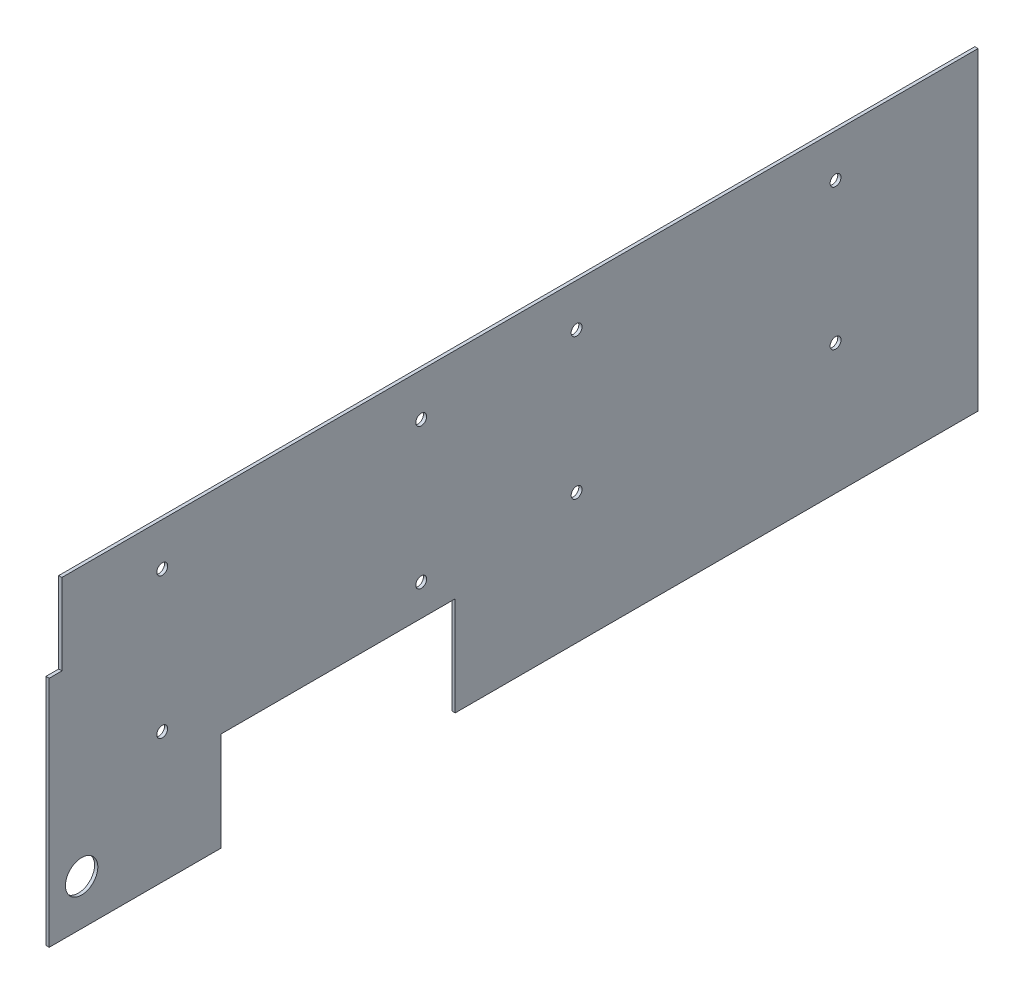
SolidWorks part; units mm, degrees
ref_plane "Front Plane" through (0, 0, 0) normal (0, 0, 1) x (1, 0, 0)
ref_plane "Top Plane" through (0, 0, 0) normal (0, 1, 0) x (1, 0, 0)
ref_plane "Right Plane" through (0, 0, 0) normal (1, 0, 0) x (0, 0, -1)
sketch "Sketch1" plane through (0, 0, 0) normal (1, 0, 0) x (0, 0, -1)
  line L1 (-227.7341, -76.9938) -> (227.7341, -76.9938)
  line L2 (-227.7341, -76.9938) -> (-227.7341, 76.9938)
  line L3 (-227.7341, 76.9938) -> (227.7341, 76.9938)
  line L4 (227.7341, -76.9938) -> (227.7341, 76.9938)
  line L5 (-227.7341, -76.9938) -> (227.7341, 76.9938) construction
  line L6 (-227.7341, 76.9938) -> (227.7341, -76.9938) construction
  point P0 (0, 0)
  dimension "D1" = 153.9875
  dimension "D2" = 455.4682
extrude "Boss-Extrude1" add sketch "Sketch1" along normal blind 1.5875
sketch "Sketch2" plane through (0, 0, 0) normal (-1, 0, 0) x (0, 0, 1)
  line L0 (221.5284, 37.3063) -> (221.5284, -76.9938)
  line L1 (227.7341, 76.9938) -> (221.5284, 76.9938)
  line L2 (227.7341, 76.9938) -> (227.7341, 37.3062)
  line L3 (227.7341, 37.3062) -> (221.5284, 37.3063)
  line L4 (221.5284, 76.9938) -> (221.5284, 37.3063)
  line L5 (227.7341, -76.9938) -> (-227.7341, -76.9938) construction
  line L6 (221.5284, 37.3063) -> (-227.7341, 37.3062)
  line L7 (-227.7341, -76.9938) -> (-227.7341, 76.9938) construction
  line L8 (143.5966, -28.5169) -> (227.7341, -28.5169)
  line L9 (143.5966, -76.9938) -> (28.6472, -76.9938)
  line L10 (143.5966, -76.9938) -> (143.5966, -28.5169)
  line L11 (143.5966, -28.5169) -> (28.6472, -28.5169)
  line L12 (28.6472, -76.9938) -> (28.6472, -28.5169)
  line L13 (227.7341, 76.9938) -> (227.7341, -76.9938) construction
  line L14 (28.6472, -28.5169) -> (-227.7341, -28.5169)
  line L15 (143.5966, -28.5169) -> (143.5966, 76.9938)
  line L16 (-227.7341, 76.9938) -> (227.7341, 76.9938) construction
  line L17 (-227.7341, -76.9938) -> (211.8591, -76.9937)
  line L18 (211.8591, -76.9937) -> (211.8591, -54.7687)
  circle A0 centre (211.8591, -54.7687) radius 7.9375
  line M14 (-227.7341, -76.9938) -> (227.7341, -76.9938)
  line M15 (227.7341, -76.9938) -> (227.7341, 76.9938)
  line M16 (227.7341, 76.9938) -> (-227.7341, 76.9938)
  dimension "D3" = 15.875
  dimension "D1" = 439.5932
  dimension "D2" = 22.225
extrude "Cut-Extrude1" cut sketch "Sketch2" against normal up to surface (1.5875 mm away) contours L12 L10 L11 M14 | L4 L3 M16 M15 | A0 region at (0, 57.15, 224.6313) region at (0, -49.3148, 206.4052) region at (0, -52.7553, 86.1219) up to face at (1.5875, 0, 0)
sketch "Sketch3" plane through (1.5875, 0, 0) normal (1, 0, 0) x (0, 0, -1)
  line L0 (227.7341, 76.9938) -> (227.7341, 55.9594)
  line L1 (227.7341, -76.9938) -> (227.7341, 76.9938) construction
  line L2 (227.7341, 55.9594) -> (157.8841, 55.9594)
  line L3 (157.8841, 55.9594) -> (30.8841, 55.9594)
  line L4 (30.8841, 55.9594) -> (-45.3159, 55.9594)
  line L5 (-45.3159, 55.9594) -> (-172.3159, 55.9594)
  line L6 (-172.3159, 55.9594) -> (-172.3159, -13.0969)
  line L7 (-172.3159, -13.0969) -> (-45.3159, -13.0969)
  line L8 (-45.3159, -13.0969) -> (30.8841, -13.0969)
  line L9 (30.8841, -13.0969) -> (157.8841, -13.0969)
  circle A0 centre (-172.3159, 55.9594) radius 2.667
  circle A1 centre (-172.3159, -13.0969) radius 2.667
  circle A2 centre (-45.3159, -13.0969) radius 2.667
  circle A3 centre (-45.3159, 55.9594) radius 2.667
  circle A4 centre (30.8841, 55.9594) radius 2.667
  circle A5 centre (30.8841, -13.0969) radius 2.667
  circle A6 centre (157.8841, 55.9594) radius 2.667
  circle A7 centre (157.8841, -13.0969) radius 2.667
  dimension "D10" = 5.334
  dimension "D11" = 5.334
  dimension "D1" = 21.0344
  dimension "D2" = 69.85
  dimension "D3" = 127
  dimension "D4" = 76.2
  dimension "D5" = 127
  dimension "D6" = 69.0563
  dimension "D7" = 127
  dimension "D8" = 76.2
  dimension "D9" = 127
  dimension "D12" = 2
  dimension "D13" = 2
  dimension "D14" = 2
extrude "Cut-Extrude2" cut sketch "Sketch3" against normal up to surface (1.5875 mm away) contours L3 A6 L2 | L2 A6 L3 | L4 A4 L3 | L3 A4 L4 | L5 A3 L4 | L4 A3 L5 | L6 A0 L5 | L5 A0 L6 | L7 A1 L6 | L6 A1 L7 | L7 A2 L8 | L8 A2 L7 | L8 A5 L9 | L9 A5 L8 | A7 region at (1.5875, 54.8275, -157.8841) region at (1.5875, 57.0913, -157.8841) region at (1.5875, -10.5053, -157.8841) region at (1.5875, -11.965, -30.8841) region at (1.5875, -14.2288, -30.8841) region at (1.5875, -11.965, 45.3159) region at (1.5875, -14.2288, 45.3159) region at (1.5875, -11.965, 171.184) region at (1.5875, -13.4742, 172.6932) region at (1.5875, 54.8275, 171.184) region at (1.5875, 56.3367, 172.6932) region at (1.5875, 54.8275, 45.3159) region at (1.5875, 57.0913, 45.3159) region at (1.5875, 54.8275, -30.8841) region at (1.5875, 57.0913, -30.8841) up to face at (0, -54.7687, 219.7966)
